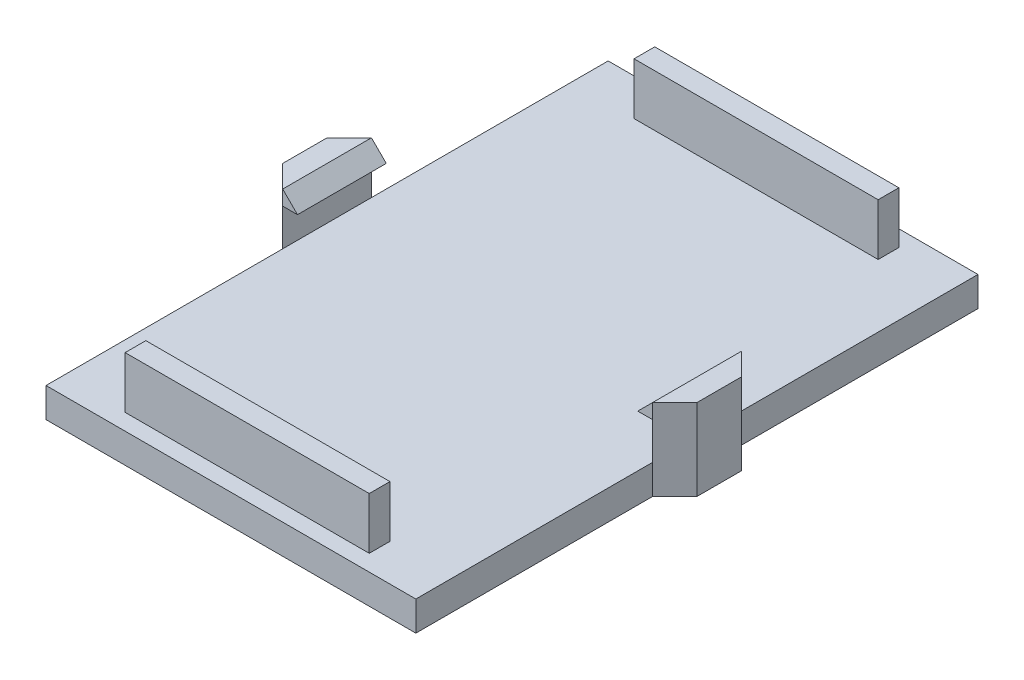
SolidWorks part; units mm, degrees
ref_plane "Front Plane" through (0, 0, 0) normal (0, 0, 1) x (1, 0, 0)
ref_plane "Top Plane" through (0, 0, 0) normal (0, 1, 0) x (1, 0, 0)
ref_plane "Right Plane" through (0, 0, 0) normal (1, 0, 0) x (0, 0, -1)
sketch "Sketch1" plane through (0, 0, 0) normal (0, 1, 0) x (1, 0, 0)
  line L0 (0, 0) -> (50000, 0) construction
  line L1 (-12.5, -19) -> (12.5, -19)
  line L2 (-12.5, -19) -> (-12.5, 19)
  line L3 (-12.5, 19) -> (12.5, 19)
  line L4 (12.5, -19) -> (12.5, 19)
  line L5 (-12.5, -19) -> (12.5, 19) construction
  line L6 (-12.5, 19) -> (12.5, -19) construction
  line L7 (0, 0) -> (0, 50000) construction
  line L8 (12.5, 3) -> (14, 1.5)
  line L9 (14, 1.5) -> (14, -1.5)
  line L10 (12.5, -3) -> (14, -1.5)
  line L11 (-12.5, -3) -> (-14, -1.5)
  line L12 (-14, 1.5) -> (-14, -1.5)
  line L13 (-12.5, 3) -> (-14, 1.5)
  line L14 (8.25, -16.5) -> (8.25, -17.9)
  line L15 (-8.25, 16.5) -> (8.25, 16.5)
  line L16 (-8.25, 16.5) -> (-8.25, 17.9)
  line L17 (-8.25, 17.9) -> (8.25, 17.9)
  line L18 (8.25, 16.5) -> (8.25, 17.9)
  line L19 (-8.25, 16.5) -> (8.25, 17.9) construction
  line L20 (-8.25, 17.9) -> (8.25, 16.5) construction
  line L21 (-8.25, -17.9) -> (8.25, -17.9)
  line L22 (-8.25, -16.5) -> (-8.25, -17.9)
  line L23 (-8.25, -16.5) -> (8.25, -16.5)
  point P0 (0, 0)
  point P15 (14, 0)
  point P20 (0, 17.2)
  dimension "D1" = 25
  dimension "D2" = 38
  dimension "D3" = 16
  dimension "D4" = 45
  dimension "D5" = 1.5
  dimension "D6" = 1.4
  dimension "D7" = 4.25
  dimension "D8" = 1.1
extrude "Boss-Extrude1" add sketch "Sketch1" along normal blind 2 contours L1 L4 L3 L2 region at (0, 0, 0)
extrude "Boss-Extrude2" add sketch "Sketch1<3>" along normal blind 5.5 contours L2 L13 L12 L11 | L4 L10 L9 L8 | L15 L18 L17 L16 | L23 L22 L21 L14 region at (-13.1667, 0, 0) region at (13.1667, 0, 0) region at (0, 0, 17.2) region at (0, 0, -17.2)
sketch "Sketch1<3>" plane through (0, 0, 0) normal (0, 1, 0) x (1, 0, 0) same geometry as "Sketch1"
sketch "Sketch2" plane through (0, 0, 0) normal (0, 0, 1) x (1, 0, 0)
  line L0 (12.5, 5.5) -> (11.5, 4.5)
  line L1 (11.5, 4.5) -> (12.5, 4.5)
  line L2 (12.5, 5.5) -> (12.5, 2) construction
  line L3 (12.5, 4.5) -> (12.5, 5.5)
  line L4 (0, -3.025) -> (0, 3.025) construction
  line L5 (-11.5, 4.5) -> (-12.5, 4.5)
  line L6 (-12.5, 4.5) -> (-12.5, 5.5)
  line L7 (-12.5, 5.5) -> (-11.5, 4.5)
  point P3 (11.7618, 4.7618)
  dimension "D1" = 1
extrude "Boss-Extrude3" add sketch "Sketch2" along normal up to vertex (3 mm away) and the other way up to vertex (3 mm away) up to point (12.5, 5.5, 3) other way up to point (12.5, 5.5, -3)
